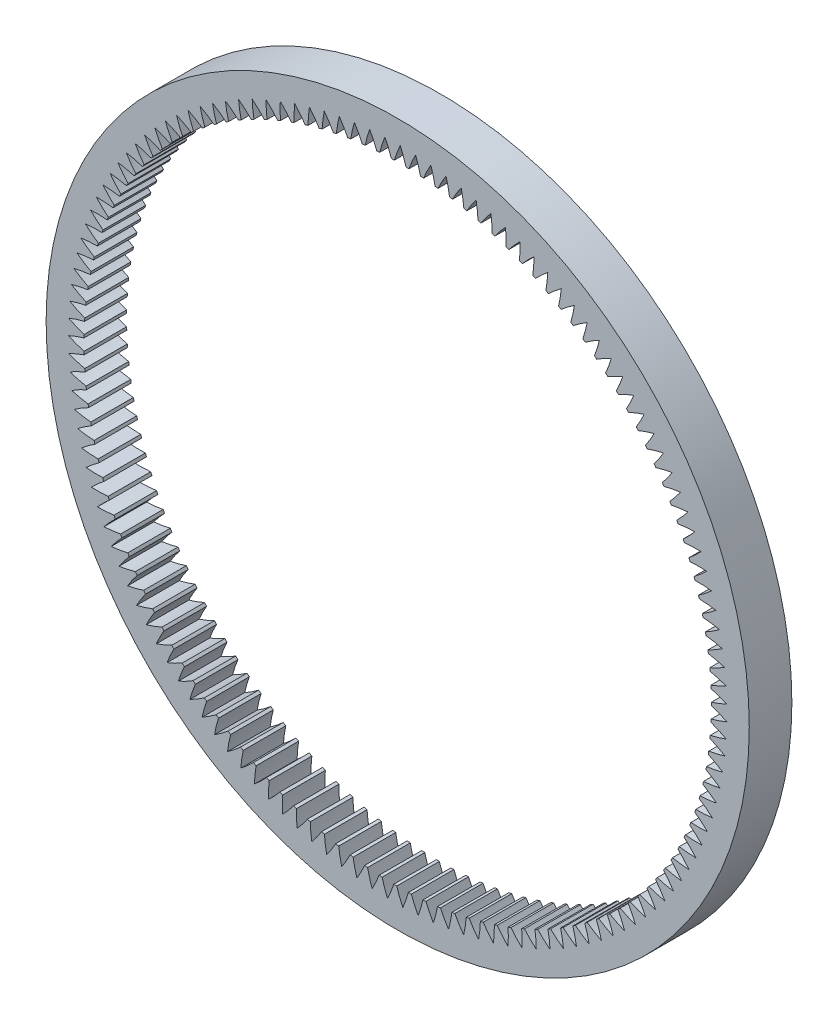
SolidWorks part; units mm, degrees
ref_plane "Front Plane" through (0, 0, 0) normal (0, 0, 1) x (1, 0, 0)
ref_plane "Top Plane" through (0, 0, 0) normal (0, 1, 0) x (1, 0, 0)
ref_plane "Right Plane" through (0, 0, 0) normal (1, 0, 0) x (0, 0, -1)
sketch "Sketch1" plane through (0, 0, 0) normal (0, 0, 1) x (1, 0, 0)
  line L0 (0, 0) -> (152.2211, 0.5826) construction
  line L1 (0, 0) -> (7.4763, 0.2026) construction
  line L2 (0, 0) -> (152.2211, 0.5826) construction
  line L3 (0, 0) -> (152.204, 2.3536) construction
  line L4 (0, 0) -> (152.0292, 7.6641) construction
  line L5 (147.2211, 0.5634) -> (164.9988, 0.6315)
  line L6 (7.4763, 0.2026) -> (164.9394, 4.4706)
  circle A0 centre (0, 0) radius 150 construction
  circle A1 centre (0, 0) radius 147.2222 construction
  circle A2 centre (0, 0) radius 140.9539 construction
  circle A3 centre (0, 0) radius 152.2222 construction
  arc A4 (147.1933, 2.9192) -> (147.2211, 0.5634) centre (0, 0) cw
  arc A5 (164.9394, 4.4706) -> (164.9988, 0.6315) centre (0, 0) cw
  spline S0 degree 4 poles (140.9539, 0) (141.047, 0.0021) (141.233, 0.0096) (141.6043, 0.0381) (142.1413, 0.0988) (142.7502, 0.1881) (143.5952, 0.3382) (144.7155, 0.5763) (146.1211, 0.9353) (148.5424, 1.6703) (151.8418, 2.9113) (156.3125, 4.9787) (161.7974, 8.1307) (167.5079, 12.0923) (173.2947, 16.8502) (178.7179, 22.0165) (183.7842, 27.5321) (188.7334, 33.6368) (194.3854, 41.5588) (200.3945, 51.493) (206.3549, 63.5923) (211.0515, 75.8366) (214.322, 86.5835) (217.006, 97.4872) (218.7638, 106.6813) (220.0572, 115.9516) (220.9004, 125.2707) (221.3104, 132.7451) (221.4993, 142.1002) (221.2188, 153.3279) (220.176, 166.3924) (218.4445, 178.4384) (216.692, 187.63) (215.3753, 193.5675) (214.7345, 196.2984) (214.1768, 198.5735) (213.7205, 200.3797) (213.2864, 202.0439) (212.8968, 203.5028) (212.5227, 204.8688) (212.2249, 205.9419) (211.8226, 207.3585) (211.531, 208.3682) (211.0466, 210.0184) (210.6618, 211.2901) (210.1884, 212.8378) (209.7547, 214.2166) (209.2845, 215.691) (208.8222, 217.1072) (208.224, 218.9088) (207.4957, 221.0461) (206.6187, 223.5443) (205.7164, 226.0241) (204.9217, 228.1477) (204.3824, 229.5564) (204.1096, 230.2614) (203.9728, 230.6129) knots 0 0 0 0 0 0.001401 0.002802 0.005604 0.008133 0.010661 0.015718 0.022839 0.02996 0.048734 0.068727 0.096889 0.125051 0.153212 0.181374 0.209535 0.237696 0.271429 0.327752 0.384075 0.440398 0.46856 0.496721 0.553044 0.581206 0.609367 0.637529 0.66569 0.722013 0.778336 0.834659 0.84874 0.86282 0.869861 0.876901 0.883942 0.890982 0.895509 0.900036 0.904564 0.909091 0.914773 0.920455 0.926136 0.931818 0.9375 0.943182 0.948864 0.954545 0.965909 0.977273 0.988636 0.994318 1 1 1 1 1 construction
  spline S1 degree 4 poles (140.9539, 0) (141.047, 0.0021) (141.233, 0.0096) (141.6043, 0.0381) (142.1413, 0.0988) (142.7502, 0.1881) (143.5952, 0.3382) (144.7155, 0.5763) (146.1211, 0.9353) (148.5424, 1.6703) (151.8418, 2.9113) (156.3125, 4.9787) (161.7974, 8.1307) (167.5079, 12.0923) (173.2947, 16.8502) (178.7179, 22.0165) (183.7842, 27.5321) (188.7334, 33.6368) (194.3854, 41.5588) (200.3945, 51.493) (206.3549, 63.5923) (211.0515, 75.8366) (214.322, 86.5835) (217.006, 97.4872) (218.7638, 106.6813) (220.0572, 115.9516) (220.9004, 125.2707) (221.3104, 132.7451) (221.4993, 142.1002) (221.2188, 153.3279) (220.176, 166.3924) (218.4445, 178.4384) (216.692, 187.63) (215.3753, 193.5675) (214.7345, 196.2984) (214.1768, 198.5735) (213.7205, 200.3797) (213.2864, 202.0439) (212.8968, 203.5028) (212.5227, 204.8688) (212.2249, 205.9419) (211.9413, 206.9407) (211.7889, 207.4725) (211.7131, 207.7353) knots 0 0 0 0 0 0.001401 0.002802 0.005604 0.008133 0.010661 0.015718 0.022839 0.02996 0.048734 0.068727 0.096889 0.125051 0.153212 0.181374 0.209535 0.237696 0.271429 0.327752 0.384075 0.440398 0.46856 0.496721 0.553044 0.581206 0.609367 0.637529 0.66569 0.722013 0.778336 0.834659 0.84874 0.86282 0.869861 0.876901 0.883942 0.890982 0.895509 0.900036 0.904564 0.909091 0.909091 0.909091 0.909091 0.909091
  point P6 (147.2046, 2.2763)
  point P14 (147.2167, 1.2764)
  point P19 (147.1933, 2.9192)
  dimension "pitchRadius" = 150
  dimension "addendumRadius" = 152.2222
  dimension "dedendumRadius" = 147.2222
  dimension "baseRadius" = 140.9539
  dimension "D1" = 1.333
  dimension "D2" = 0.667
  dimension "toothArc" = 2.667
  dimension "backlash" = 1
  dimension "D3" = 165
extrude "Boss-Extrude1" add sketch "Sketch1" along normal blind 20 contours S1 region at (157.5547, 2.2775, 0)
mirror "Mirror1" about plane through (0, 0, 20) normal (-0.0271, 0.9996, 0) of "Boss-Extrude1"
pattern_circular "CirPattern2" count 135 over 360 about axis through (0, 0, 20) along (0, 0, -1) of "Boss-Extrude1", "Mirror1"
ref_axis "Axis1" through (0, 0, 0) along (0, 0, 1)
equation "\"D2@Sketch1\"=\"toothArc@Sketch1\"/4"
equation "\"pitchRadius\"= 15"
equation "\"nTeeth\"= 135"
equation "\"pressureAngle\"= 20"
equation "\"baseRadius\"= \"pitchRadius\" * cos ( \"pressureAngle\" )"
equation "\"diametralPitch\"= \"nTeeth\" / ( 2 * \"pitchRadius\" )'note units: cm^-1"
equation "\"dedendum\"= 1.25 / \"diametralPitch\"'for full depth, 20 deg pressure angle"
equation "\"addendum\"= 1 / \"diametralPitch\""
equation "\"pitchRadius@Sketch1\"= \"pitchRadius\""
equation "\"addendumRadius@Sketch1\"= \"pitchRadius\" + \"addendum\""
equation "\"dedendumRadius@Sketch1\"= \"pitchRadius\" - \"dedendum\""
equation "\"baseRadius@Sketch1\"= \"baseRadius\""
equation "\"D2@CirPattern2\"= \"nTeeth\""
equation "\"D1@CirPattern2\"=\"nTeeth\""
equation "\"toothArc@Sketch1\"=360/\"nTeeth\""
equation "\"D1@Sketch1\"=\"toothArc@Sketch1\"/2"
